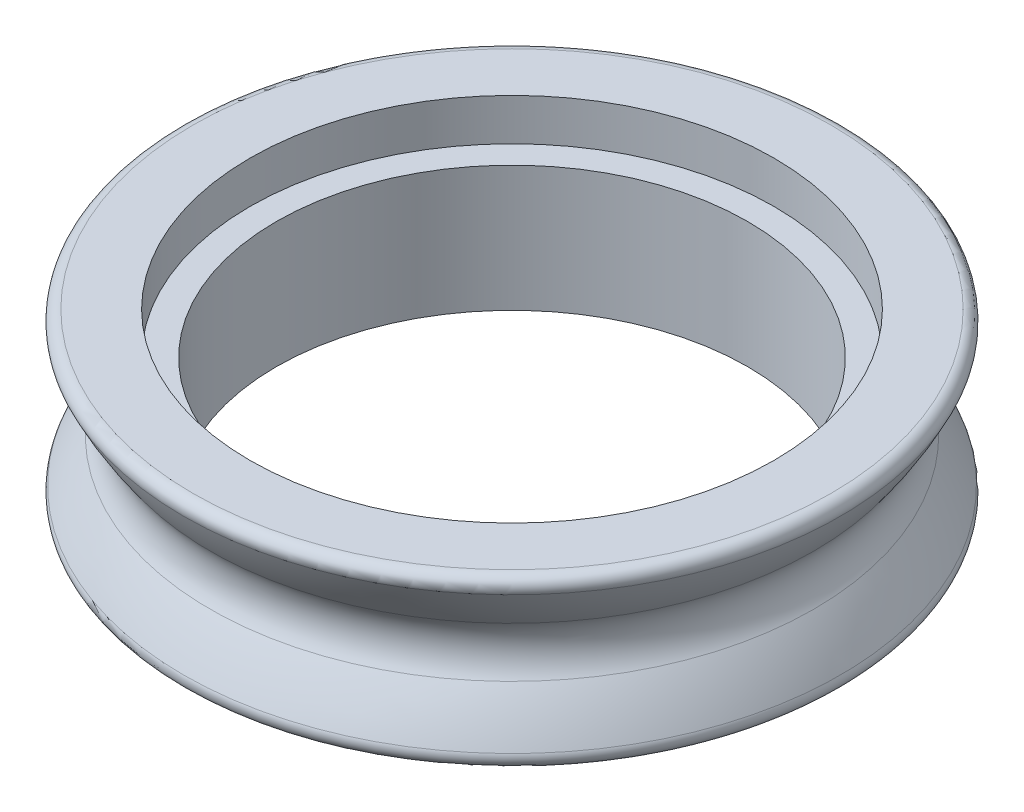
SolidWorks part; units mm, degrees
ref_plane "Front Plane" through (0, 0, 0) normal (0, 0, 1) x (1, 0, 0)
ref_plane "Top Plane" through (0, 0, 0) normal (0, 1, 0) x (1, 0, 0)
ref_plane "Right Plane" through (0, 0, 0) normal (1, 0, 0) x (0, 0, -1)
sketch "Sketch1" plane through (0, 0, 0) normal (0, 0, 1) x (1, 0, 0)
  line L0 (0, 5.08) -> (0, -5.08) construction
  line L1 (14.2875, 5.08) -> (14.2875, -5.08)
  line L2 (14.2875, -5.08) -> (20.32, -5.08)
  line L3 (20.32, -5.08) -> (20.32, -2.54)
  line L4 (0, 0) -> (20.32, 0) construction
  line L5 (20.32, 5.08) -> (20.32, 2.54)
  line L6 (14.2875, 5.08) -> (20.32, 5.08)
  arc A0 (20.32, 2.54) -> (20.32, -2.54) centre (20.32, 0) ccw
  point P13 (14.2875, 0)
  dimension "D5" = 2.54
  dimension "D1" = 10.16
  dimension "D2" = 40.64
  dimension "D4" = 28.575
revolve "Revolve1" add sketch "Sketch1" angle 360 about L0
fillet "Fillet1" radius 16.51 2 edges at (0, -2.54, 20.32) (0, 2.54, 20.32)
fillet "Fillet2" radius 0.635 2 edges at (0, -5.08, 20.32) (0, 5.08, 20.32)
sketch "Sketch2" plane through (0, 5.08, 0) normal (0, 1, 0) x (1, 0, 0)
  circle A0 centre (0, 0) radius 15.875
  dimension "D1" = 31.75
extrude "Cut-Extrude1" cut sketch "Sketch2" against normal blind 2.54
